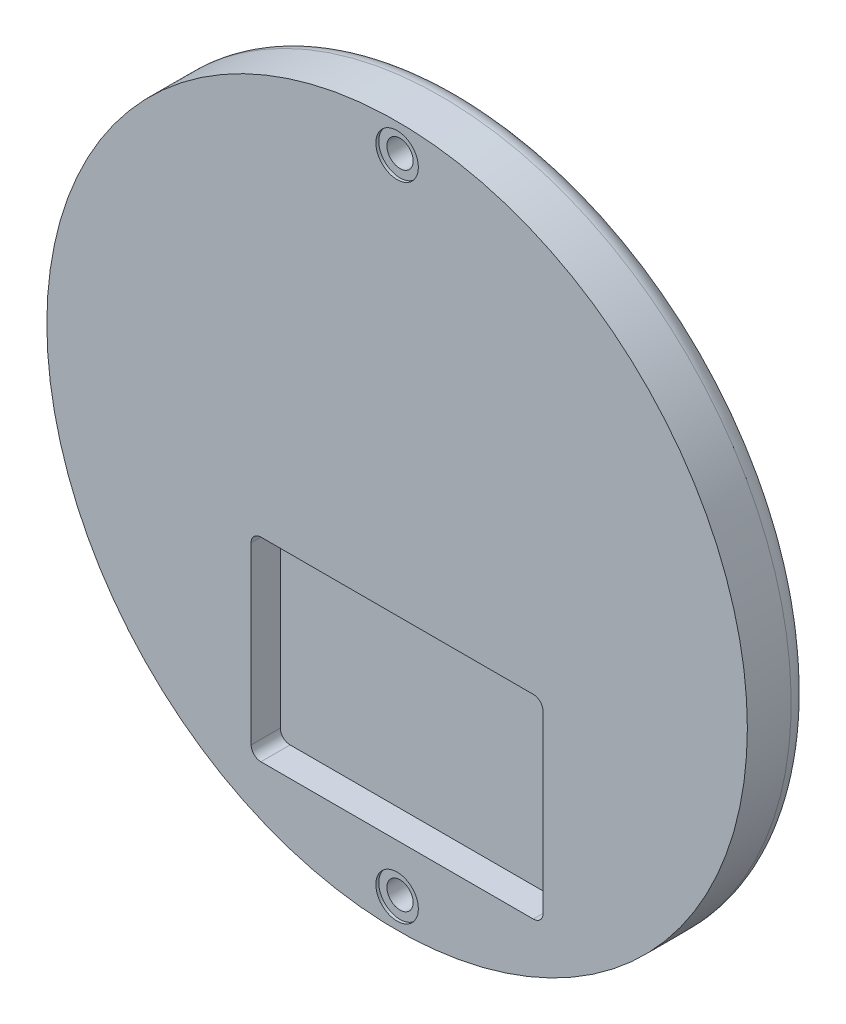
SolidWorks part; units mm, degrees
ref_plane "Front Plane" through (0, 0, 0) normal (0, 0, 1) x (1, 0, 0)
ref_plane "Top Plane" through (0, 0, 0) normal (0, 1, 0) x (1, 0, 0)
ref_plane "Right Plane" through (0, 0, 0) normal (1, 0, 0) x (0, 0, -1)
sketch "Sketch1" plane through (0, 0, 0) normal (0, 0, 1) x (1, 0, 0)
  circle A0 centre (0, 0) radius 36
  dimension "D1" = 72
extrude "Boss-Extrude1" add sketch "Sketch1" along normal blind 6.5
sketch "Sketch2" plane through (0, 0, 0) normal (0, 0, -1) x (-1, 0, 0)
  line L0 (0, 36) -> (0, -36) construction
  line L1 (-36, 0) -> (36, 0) construction
  circle A0 centre (0, 0) radius 36 construction
  circle A1 centre (0, 0) radius 33 construction
  circle A2 centre (0, 33) radius 1.9844
  circle A3 centre (0, -33) radius 1.9844
  dimension "D1" = 66
  dimension "D2" = 3.9688
hole_wizard "#4-40 Tapped Hole1" positions "Sketch9" profile "Sketch10" tap size "#4-40" standard "ANSI Inch"
sketch "Sketch9" plane through (0, 0, 0) normal (0, 0, -1) x (-1, 0, 0)
  point P0 (0, -33)
cosmetic thread "Hole Thread1" parameters "D1"=5.69, "D2"=2.8448
sketch "Sketch10" plane through (0, -33, 0) normal (1, 0, 0) x (0, 1, 0)
  line L0 (0, 0) -> (0, 7.3112)
  line L1 (0, 7.3112) -> (1.35, 6.5)
  line L2 (1.35, 6.5) -> (1.35, 1.1328)
  line L3 (1.35, 1.1328) -> (2.7, 0)
  line L5 (2.7, 0) -> (0, 0)
  line L6 (-1.35, 1.1328) -> (-2.7, 0) construction
  line L10 (0, 7.3112) -> (-1.35, 6.5) construction
  line L11 (0, -6.35) -> (0, 107.95) construction
  dimension "Tap Drill Dia." = 2.7
  dimension "Tap Drill Depth" = 6.5
  dimension "Near C'Sink Dia." = 5.4
  dimension "Near C'Sink Angle" = 100
  dimension "Drill Angle" = 118
sketch "Sketch11" plane through (0, 0, 6.5) normal (0, 0, 1) x (1, 0, 0)
  circle A0 centre (0, -33) radius 2.1844
  dimension "D1" = 4.3688
extrude "Cut-Extrude3" cut sketch "Sketch11" against normal blind 0.3
ref_plane "Plane2" through (0, 0, 0) normal (0, -1, 0) x (-1, 0, 0)
mirror "Mirror1" about plane through (0, 0, 0) normal (0, -1, 0) of "Cut-Extrude3", "#4-40 Tapped Hole1"
fillet "Fillet1" radius 2 1 edges at (36, 0, 0)
sketch "Sketch12" plane through (0, 0, 6.5) normal (0, 0, 1) x (1, 0, 0)
  line L0 (0, 36) -> (0, -36) construction
  line L1 (14, -8) -> (-14, -8)
  line L2 (15, -9) -> (15, -27)
  line L3 (14, -28) -> (-14, -28)
  line L4 (-15, -9) -> (-15, -27)
  line L5 (15, -8) -> (-15, -28) construction
  line L6 (15, -28) -> (-15, -8) construction
  arc A0 (14, -8) -> (15, -9) centre (14, -9) cw
  arc A1 (15, -27) -> (14, -28) centre (14, -27) cw
  arc A2 (-14, -28) -> (-15, -27) centre (-14, -27) cw
  arc A3 (-14, -8) -> (-15, -9) centre (-14, -9) ccw
  point P0 (0, -18)
  dimension "D4" = 1
  dimension "D1" = 5
  dimension "D2" = 20
  dimension "D3" = 30
extrude "Cut-Extrude4" cut sketch "Sketch12" against normal blind 3
